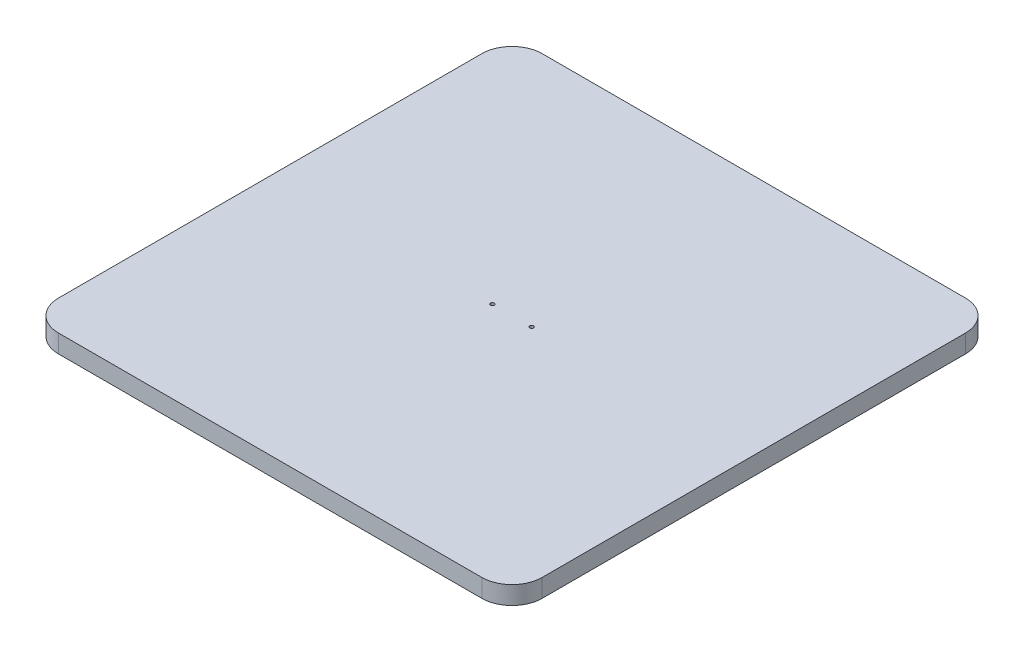
SolidWorks part; units mm, degrees
ref_plane "Front Plane" through (0, 0, 0) normal (0, 0, 1) x (1, 0, 0)
ref_plane "Top Plane" through (0, 0, 0) normal (0, 1, 0) x (1, 0, 0)
ref_plane "Right Plane" through (0, 0, 0) normal (1, 0, 0) x (0, 0, -1)
sketch "Sketch1" plane through (0, 0, 0) normal (0, 1, 0) x (1, 0, 0)
  line L1 (80, 80) -> (-80, 80)
  line L2 (80, 80) -> (80, -80)
  line L3 (80, -80) -> (-80, -80)
  line L4 (-80, 80) -> (-80, -80)
  line L5 (80, 80) -> (-80, -80) construction
  line L6 (80, -80) -> (-80, 80) construction
  point P0 (0, 0)
  dimension "D1" = 160
  dimension "D2" = 160
extrude "Boss-Extrude1" add sketch "Sketch1" along normal blind 6
hole_wizard "M1.6 Tapped Hole1" positions "Sketch3" profile "Sketch4" tap size "M1.6" standard "ISO" end condition through all
sketch "Sketch3" plane through (0, 6, 0) normal (0, 1, 0) x (1, 0, 0)
  line L0 (-80, 0) -> (80, 0)
  line L1 (-80, 80) -> (-80, -80) construction
  line L2 (80, -80) -> (80, 80) construction
  point P7 (-6.5, 0)
  point P9 (6.5, 0)
  dimension "D1" = 6.5
  dimension "D2" = 6.5
sketch "Sketch4" plane through (6.5, 6, 0) normal (1, 0, 0) x (0, 0, 1)
  line L0 (0, 0) -> (0, 6)
  line L1 (0, 6) -> (0.625, 6)
  line L2 (0.625, 6) -> (0.625, 0)
  line L5 (0.625, 0) -> (0, 0)
  line L11 (0, -6.35) -> (0, 107.95) construction
  dimension "Thru Tap Drill Dia." = 1.25
  dimension "Thru Tap Drill Depth" = 6
cosmetic thread "Hole Thread5" parameters "D1"=10, "D2"=2.25
cosmetic thread "Hole Thread6" parameters "D1"=10, "D2"=2.25
sketch "Sketch5" plane through (0, 6, 0) normal (0, 1, 0) x (1, 0, 0)
  line L1 (20, 20) -> (-20, 20)
  line L2 (20, 20) -> (20, -20)
  line L3 (20, -20) -> (-20, -20)
  line L4 (-20, 20) -> (-20, -20)
  line L5 (20, 20) -> (-20, -20) construction
  line L6 (20, -20) -> (-20, 20) construction
  point P0 (0, 0)
  dimension "D1" = 40
  dimension "D2" = 40
extrude "Boss-Extrude2" [suppressed] add sketch "Sketch5" along normal blind 10
fillet "Fillet1" radius 10 4 edges at (-80, 3, 80) (80, 3, 80) (80, 3, -80) (-80, 3, -80)
